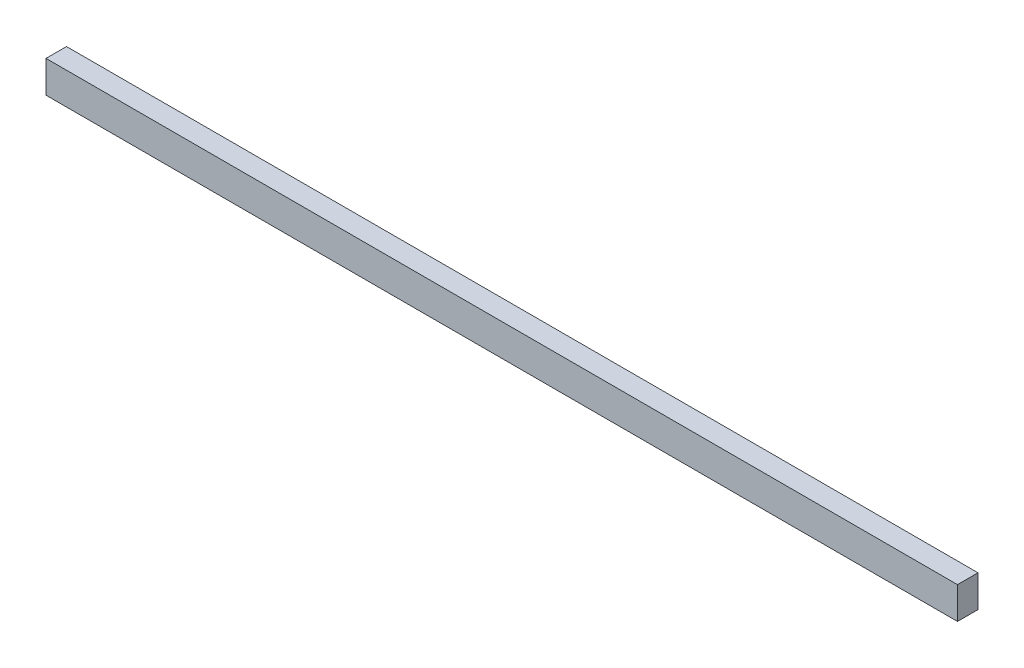
SolidWorks part; units mm, degrees
material "Pine"
ref_plane "Front Plane" through (0, 0, 0) normal (0, 0, 1) x (1, 0, 0)
ref_plane "Top Plane" through (0, 0, 0) normal (0, 1, 0) x (1, 0, 0)
ref_plane "Right Plane" through (0, 0, 0) normal (1, 0, 0) x (0, 0, -1)
sketch "Sketch1" plane through (0, 0, 0) normal (1, 0, 0) x (0, 0, -1)
  line L1 (0, 0) -> (45, 0)
  line L2 (0, 0) -> (0, -70)
  line L3 (0, -70) -> (45, -70)
  line L4 (45, 0) -> (45, -70)
  dimension "D1" = 70
  dimension "D2" = 45
extrude "Boss-Extrude1" add sketch "Sketch1" along normal blind 2000
